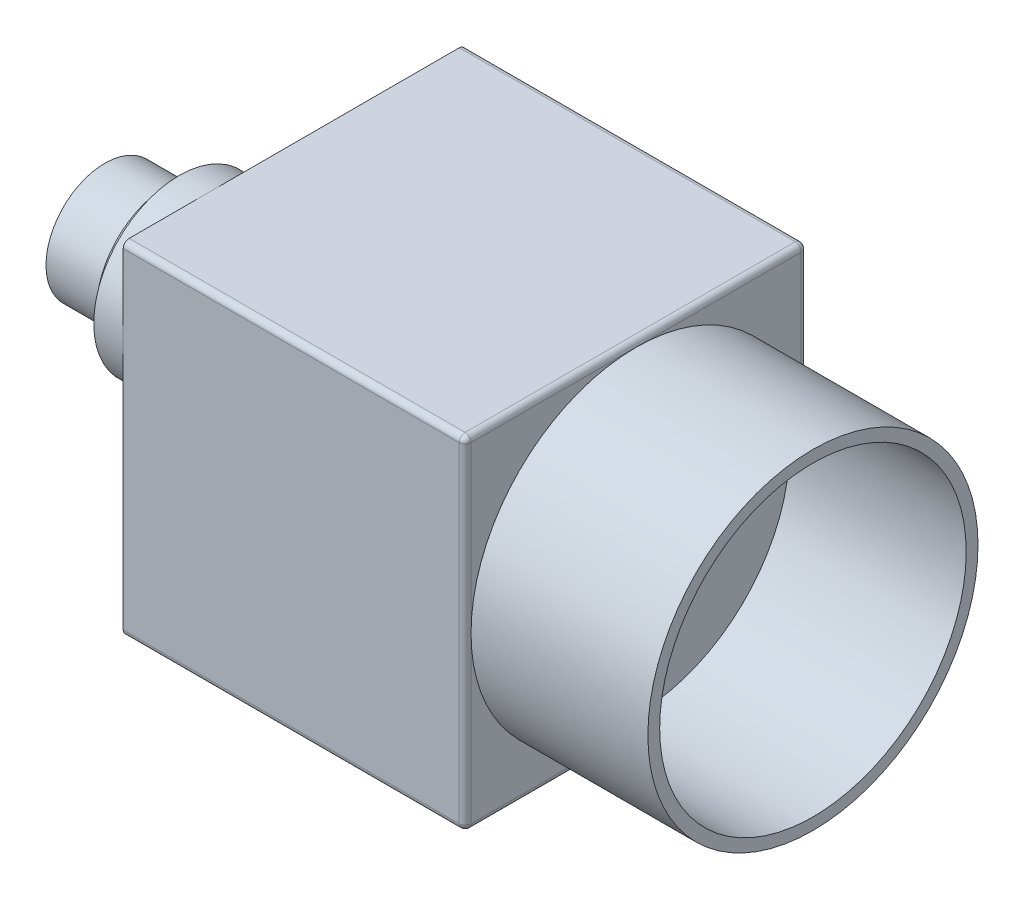
SolidWorks part; units mm, degrees
ref_plane "前视基准面" through (0, 0, 0) normal (0, 0, 1) x (1, 0, 0)
ref_plane "上视基准面" through (0, 0, 0) normal (0, 1, 0) x (1, 0, 0)
ref_plane "右视基准面" through (0, 0, 0) normal (1, 0, 0) x (0, 0, -1)
sketch "草图1" plane through (0, 0, 0) normal (1, 0, 0) x (0, 0, -1)
  line L1 (-14.5, -14.5) -> (14.5, -14.5)
  line L2 (-14.5, -14.5) -> (-14.5, 14.5)
  line L3 (-14.5, 14.5) -> (14.5, 14.5)
  line L4 (14.5, -14.5) -> (14.5, 14.5)
  line L5 (-14.5, -14.5) -> (14.5, 14.5) construction
  line L6 (-14.5, 14.5) -> (14.5, -14.5) construction
  point P0 (0, 0)
  dimension "D1" = 29
  dimension "D2" = 29
extrude "凸台-拉伸1" add sketch "草图1" along normal blind 29
sketch "草图3" plane through (0, 0, 0) normal (-1, 0, 0) x (0, 0, 1)
  line L0 (-14.5, 14.5) -> (14.5, 14.5) construction
  line L1 (-11.35, -4.1) -> (11.35, -4.1)
  line L2 (-11.35, -4.1) -> (-11.35, -13.1)
  line L3 (-11.35, -13.1) -> (11.35, -13.1)
  line L4 (11.35, -4.1) -> (11.35, -13.1)
  line L5 (-11.35, -4.1) -> (11.35, -13.1) construction
  line L6 (-11.35, -13.1) -> (11.35, -4.1) construction
  point P0 (0, -8.6)
  dimension "D1" = 0
  dimension "D2" = 22.7
  dimension "D3" = 18.6
  dimension "D4" = 9
extrude "凸台-拉伸3" add sketch "草图3" along normal blind 1
sketch "草图4" plane through (-1, 0, 0) normal (-1, 0, 0) x (0, 0, 1)
  line L0 (-11.35, -13.1) -> (11.35, -13.1) construction
  line L2 (-7, -7.1) -> (7, -7.1)
  line L3 (-7, -7.1) -> (-7, -10.1)
  line L4 (-7, -10.1) -> (7, -10.1)
  line L5 (7, -7.1) -> (7, -10.1)
  line L6 (-7, -7.1) -> (7, -10.1) construction
  line L7 (-7, -10.1) -> (7, -7.1) construction
  line L8 (-6.5, -7.6) -> (6.5, -7.6)
  line L9 (-6.5, -7.6) -> (-6.5, -9.6)
  line L10 (-6.5, -9.6) -> (6.5, -9.6)
  line L11 (6.5, -7.6) -> (6.5, -9.6)
  line L12 (-6.5, -7.6) -> (6.5, -9.6) construction
  line L13 (-6.5, -9.6) -> (6.5, -7.6) construction
  circle A0 centre (-9, -8.6) radius 1
  circle A1 centre (9, -8.6) radius 1
  point P7 (0, -8.6)
  point P12 (0, -8.6)
  dimension "D1" = 9
  dimension "D2" = 9
  dimension "D4" = 4.5
  dimension "D5" = 2
  dimension "D6" = 2
  dimension "D12" = 9
  dimension "D3" = 4.5
  dimension "D7" = 14
  dimension "D8" = 3
  dimension "D9" = 0.5
  dimension "D10" = 0.5
  dimension "D11" = 0
extrude "凸台-拉伸4" add sketch "草图4" along normal blind 1
sketch "草图5" plane through (0, 0, 0) normal (-1, 0, 0) x (0, 0, 1)
  line L0 (-14.5, 14.5) -> (14.5, 14.5) construction
  line L1 (14.5, 14.5) -> (14.5, -14.5) construction
  circle A0 centre (7.25, 7.25) radius 7.25
  dimension "D1" = 14.5
extrude "凸台-拉伸5" add sketch "草图5" along normal blind 2.5
sketch "草图6" plane through (-2.5, 0, 0) normal (-1, 0, 0) x (0, 0, 1)
  circle A0 centre (7.25, 7.25) radius 6
  dimension "D1" = 12
extrude "凸台-拉伸6" add sketch "草图6" along normal blind 1
sketch "草图7" plane through (-3.5, 0, 0) normal (-1, 0, 0) x (0, 0, 1)
  circle A0 centre (7.25, 7.25) radius 5
extrude "凸台-拉伸7" add sketch "草图7" along normal blind 5.3
sketch "草图8" plane through (29, 0, 0) normal (1, 0, 0) x (0, 0, -1)
  circle A0 centre (0, 0) radius 14
  circle A1 centre (0, 0) radius 13
  dimension "D1" = 28
  dimension "D2" = 26
extrude "凸台-拉伸8" add sketch "草图8" along normal blind 15
sketch "草图9" plane through (0, -14.5, 0) normal (0, -1, 0) x (1, 0, 0)
  line L0 (0, 14.5) -> (0, -14.5) construction
  circle A0 centre (3, 0) radius 1.5
  circle A1 centre (26.7, -10) radius 1.5
  circle A2 centre (26.7, 10) radius 1.5
  dimension "D1" = 3
  dimension "D2" = 3
  dimension "D3" = 0
  dimension "D4" = 3
  dimension "D5" = 23.7
  dimension "D6" = 23.7
  dimension "D7" = 3
  dimension "D8" = 10
  dimension "D9" = 10
hole_wizard "M3 螺纹孔1" positions "草图10" profile "草图12" tap size "M3" standard "GB"
sketch "草图10" plane through (0, -14.5, 0) normal (0, -1, 0) x (-1, 0, 0)
  point P0 (-26.7, 10)
  point P3 (-26.7, -10)
  point P6 (-3, 0)
sketch "草图12" plane through (26.7, -14.5, -10) normal (1, 0, 0) x (0, 0, -1)
  line L0 (0, 0) -> (0, 4.9511)
  line L1 (0, 4.9511) -> (1.25, 4.2)
  line L2 (1.25, 4.2) -> (1.25, 0)
  line L5 (1.25, 0) -> (0, 0)
  line L10 (0, 4.9511) -> (-1.25, 4.2) construction
  line L11 (0, -6.35) -> (0, 107.95) construction
  dimension "螺纹孔钻头直径" = 2.5
  dimension "螺纹孔钻头深度" = 4.2
  dimension "导头角度" = 118
cosmetic thread "孔螺蚊线1" parameters "D1"=2.7, "D2"=3
cosmetic thread "孔螺蚊线2" parameters "D1"=2.7, "D2"=3
cosmetic thread "孔螺蚊线3" parameters "D1"=2.7, "D2"=3
fillet "圆角1" radius 0.5 8 edges at (14.5, -14.5, 14.5) (29, -14.5, 0) (14.5, -14.5, -14.5) (29, 0, -14.5) (29, 0, 14.5) (29, 14.5, 0) (14.5, 14.5, 14.5) (14.5, 14.5, -14.5)
